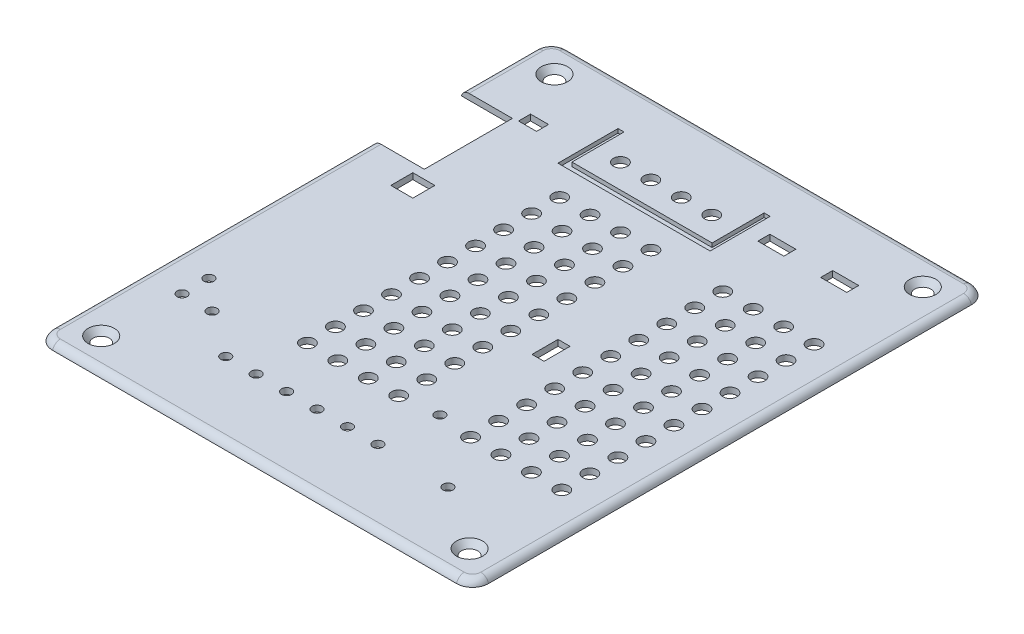
SolidWorks part; units mm, degrees
ref_plane "Přední rovina" through (0, 0, 0) normal (0, 0, 1) x (1, 0, 0)
ref_plane "Horní rovina" through (0, 0, 0) normal (0, 1, 0) x (1, 0, 0)
ref_plane "Pravá rovina" through (0, 0, 0) normal (1, 0, 0) x (0, 0, -1)
sketch "Skica1" plane through (0, 0, 0) normal (0, 1, 0) x (1, 0, 0)
  line L1 (-54.445, -64.3) -> (54.445, -64.3)
  line L2 (-54.445, -64.3) -> (-54.445, 64.3)
  line L3 (-54.445, 64.3) -> (54.445, 64.3)
  line L4 (54.445, -64.3) -> (54.445, 64.3)
  line L5 (-54.445, -64.3) -> (54.445, 64.3) construction
  line L6 (-54.445, 64.3) -> (54.445, -64.3) construction
  point P0 (0, 0)
  dimension "D1" = 108.89
  dimension "D2" = 128.6
extrude "Přidat vysunutím1" add sketch "Skica1" along normal blind 1.5
fillet "Zaoblit1" radius 4 4 edges at (54.445, 0.75, -64.3) (54.445, 0.75, 64.3) (-54.445, 0.75, -64.3) (-54.445, 0.75, 64.3)
fillet "Zaoblit2" radius 2 8 edges at (53.2734, 1.5, 63.1284) (0, 1.5, 64.3) (-53.2734, 1.5, 63.1284) (-54.445, 1.5, 0) (-53.2734, 1.5, -63.1284) (0, 1.5, -64.3) (53.2734, 1.5, -63.1284) (54.445, 1.5, 0)
sketch "Skica2" plane through (0, 0, 0) normal (0, -1, 0) x (1, 0, 0)
  line L0 (0, 68.8192) -> (0, -71.6902) construction
  line L1 (-80.8942, 0) -> (91.0271, 0) construction
  circle A0 centre (-46, 56.6) radius 1.6
  dimension "D1" = 3.2
  dimension "D2" = 46
  dimension "D3" = 56.6
extrude "Odebrat vysunutím1" cut sketch "Skica2" against normal blind 3
pattern_linear "LinPole1" count 2 spacing 113.2 along (0, 0, -1) count 2 spacing 92 along (1, 0, 0) of "Odebrat vysunutím1"
chamfer "Zkosení1" distance 2 angle 40 4 edges at (46, 1.5, 55) (46, 1.5, -58.2) (-46, 1.5, -58.2) (-46, 1.5, 55) first distance on face at (46, 0, 55) first distance on face at (46, 0, -58.2) first distance on face at (-46, 0, -58.2) first distance on face at (-46, 0, 55)
sketch "Skica3" plane through (0, 1.5, 0) normal (0, 1, 0) x (1, 0, 0)
  line L3 (-50, -50) -> (50, -50) construction
  line L4 (-50, -50) -> (-50, 50) construction
  line L5 (-50, 50) -> (50, 50) construction
  line L6 (50, -50) -> (50, 50) construction
  line L7 (-50, -50) -> (50, 50) construction
  line L8 (-50, 50) -> (50, -50) construction
  circle A0 centre (44.83, -32.38) radius 1.75
  circle A1 centre (4.08, -32.38) radius 1.75
  circle A2 centre (4.08, 45.8) radius 1.75
  point P7 (0, 0)
  dimension "D2" = 3.5
  dimension "D6" = 3.5
  dimension "D11" = 3.5
  dimension "D1" = 5.17
  dimension "D3" = 17.62
  dimension "D4" = 100
  dimension "D5" = 100
  dimension "D7" = 45.92
  dimension "D8" = 17.62
  dimension "D9" = 45.92
  dimension "D10" = 4.2
extrude "Odebrat vysunutím3" cut sketch "Skica3" against normal blind 4 contours A0 region at (44.83, 1.5, 32.38)
pattern_linear "LinPole3" count 10 spacing 7 along (0, 0, -1) count 4 spacing 7.6 along (-1, 0, 0) of "Odebrat vysunutím3"
extrude "Odebrat vysunutím4" cut sketch "Skica3<3>" against normal blind 4 contours A1 region at (4.08, 1.5, 32.38)
sketch "Skica3<3>" plane through (0, 1.5, 0) normal (0, 1, 0) x (1, 0, 0) same geometry as "Skica3"
pattern_linear "LinPole4" count 10 spacing 7 along (0, 0, -1) count 4 spacing 7.6 along (-1, 0, 0) of "Odebrat vysunutím4"
extrude "Odebrat vysunutím5" cut sketch "Skica3<4>" against normal blind 10
sketch "Skica3<4>" plane through (0, 1.5, 0) normal (0, 1, 0) x (1, 0, 0) same geometry as "Skica3"
pattern_linear "LinPole5" count 4 spacing 7.6 along (-1, 0, 0) of "Odebrat vysunutím5"
sketch "Skica4" plane through (0, 1.5, 0) normal (0, 1, 0) x (1, 0, 0)
  line L1 (-50, -50) -> (50, -50) construction
  line L2 (-50, -50) -> (-50, 50) construction
  line L3 (-50, 50) -> (50, 50) construction
  line L4 (50, -50) -> (50, 50) construction
  line L5 (-50, -50) -> (50, 50) construction
  line L6 (-50, 50) -> (50, -50) construction
  line L7 (15.5, 48.9) -> (22, 48.9)
  line L8 (15.5, 48.9) -> (15.5, 45.9)
  line L9 (15.5, 45.9) -> (22, 45.9)
  line L10 (22, 48.9) -> (22, 45.9)
  line L11 (15.5, 48.9) -> (22, 45.9) construction
  line L12 (15.5, 45.9) -> (22, 48.9) construction
  line L13 (31.2, 48.9) -> (37.7, 48.9)
  line L14 (31.2, 48.9) -> (31.2, 45.9)
  line L15 (31.2, 45.9) -> (37.7, 45.9)
  line L16 (37.7, 48.9) -> (37.7, 45.9)
  line L17 (31.2, 48.9) -> (37.7, 45.9) construction
  line L18 (31.2, 45.9) -> (37.7, 48.9) construction
  line L19 (11.8, -0.3) -> (14.8, -0.3)
  line L20 (11.8, -0.3) -> (11.8, -6.8)
  line L21 (11.8, -6.8) -> (14.8, -6.8)
  line L22 (14.8, -0.3) -> (14.8, -6.8)
  line L23 (11.8, -0.3) -> (14.8, -6.8) construction
  line L24 (11.8, -6.8) -> (14.8, -0.3) construction
  circle A0 centre (13.38, -31.4) radius 1.25
  circle A2 centre (30, -46) radius 1.25
  circle A3 centre (-45, -37.4) radius 1.25
  circle A4 centre (-45, -30.7) radius 1.25
  circle A5 centre (-37.52, -37.4) radius 1.25
  point P0 (0, 0)
  point P6 (18.75, 47.4)
  point P11 (34.45, 47.4)
  point P16 (13.3, -3.55)
  point P21 (13.3, -0.3)
  dimension "D13" = 2.5
  dimension "D16" = 12.48
  dimension "D17" = 2.5
  dimension "D23" = 2.5
  dimension "D24" = 2.5
  dimension "D25" = 2.5
  dimension "D1" = 100
  dimension "D2" = 100
  dimension "D3" = 3
  dimension "D4" = 6.5
  dimension "D5" = 1.1
  dimension "D6" = 1.1
  dimension "D7" = 12.3
  dimension "D8" = 28
  dimension "D9" = 35.2
  dimension "D10" = 50.3
  dimension "D11" = 36.62
  dimension "D12" = 18.6
  dimension "D14" = 5
  dimension "D15" = 5
  dimension "D18" = 20
  dimension "D19" = 4
  dimension "D20" = 80.7
  dimension "D21" = 87.4
  dimension "D22" = 87.4
extrude "Odebrat vysunutím6" cut sketch "Skica4" against normal blind 10
sketch "Skica5" plane through (0, 1.5, 0) normal (0, 1, 0) x (1, 0, 0)
  line L1 (-50, 50) -> (50, 50) construction
  line L2 (-50, 50) -> (-50, -50) construction
  line L3 (-50, -50) -> (50, -50) construction
  line L4 (50, 50) -> (50, -50) construction
  line L5 (-50, 50) -> (50, -50) construction
  line L6 (-50, -50) -> (50, 50) construction
  circle A0 centre (-26, -45.5) radius 1.25
  point P0 (0, 0)
  dimension "D5" = 2.5
  dimension "D1" = 100
  dimension "D2" = 100
  dimension "D3" = 4.5
  dimension "D4" = 76
extrude "Odebrat vysunutím7" cut sketch "Skica5" against normal blind 10
pattern_linear "LinPole6" count 6 spacing 7.6 along (1, 0, 0) of "Odebrat vysunutím7"
sketch "Skica6" plane through (0, 1.5, 0) normal (0, 1, 0) x (1, 0, 0)
  line L1 (-42.39, 17.62) -> (-36.89, 17.62)
  line L2 (-42.39, 17.62) -> (-42.39, 12.12)
  line L3 (-42.39, 12.12) -> (-36.89, 12.12)
  line L4 (-36.89, 17.62) -> (-36.89, 12.12)
  line L5 (-42.39, 17.62) -> (-36.89, 12.12) construction
  line L6 (-42.39, 12.12) -> (-36.89, 17.62) construction
  line L7 (-41.7, 41.8) -> (-63.2133, 41.8)
  line L8 (-41.7, 41.8) -> (-41.7, 19.8)
  line L9 (-41.7, 19.8) -> (-63.2133, 19.8)
  line L10 (-63.2133, 41.8) -> (-63.2133, 19.8)
  line L11 (-41.7, 41.8) -> (-63.2133, 19.8) construction
  line L12 (-41.7, 19.8) -> (-63.2133, 41.8) construction
  line L14 (-50, 50) -> (50, 50) construction
  line L15 (-50, 50) -> (-50, -50) construction
  line L16 (-50, -50) -> (50, -50) construction
  line L17 (50, 50) -> (50, -50) construction
  line L18 (-50, 50) -> (50, -50) construction
  line L19 (-50, -50) -> (50, 50) construction
  line L20 (-40.37, 45) -> (-35.87, 45)
  line L21 (-40.37, 45) -> (-40.37, 42)
  line L22 (-40.37, 42) -> (-35.87, 42)
  line L23 (-35.87, 45) -> (-35.87, 42)
  line L24 (-40.37, 45) -> (-35.87, 42) construction
  line L25 (-40.37, 42) -> (-35.87, 45) construction
  point P0 (-39.64, 14.87)
  point P5 (-52.4567, 30.8)
  point P10 (-63.2133, 19.8)
  point P12 (0, 0)
  point P18 (-52.4567, 41.8)
  point P20 (-38.12, 43.5)
  dimension "D1" = 100
  dimension "D2" = 100
  dimension "D3" = 10.36
  dimension "D4" = 35.13
  dimension "D5" = 5.5
  dimension "D6" = 8.2
  dimension "D7" = 30.2
  dimension "D8" = 8.3
  dimension "D9" = 6.5
  dimension "D10" = 11.88
  dimension "D11" = 4.5
  dimension "D12" = 3
extrude "Odebrat vysunutím8" cut sketch "Skica6" against normal blind 10 contours L4 L1 L2 L3 | L23 L20 L21 L22 | L7 L10 L9 L8 region at (-39.64, 1.5, -14.87) region at (-38.12, 1.5, -43.5)
sketch "Skica7" plane through (0, 1.5, 0) normal (0, 1, 0) x (1, 0, 0)
  line L1 (-24.82, 39.8) -> (10.18, 39.8)
  line L2 (-24.82, 39.8) -> (-24.82, 37.8)
  line L3 (-24.82, 37.8) -> (10.18, 37.8)
  line L4 (10.18, 39.8) -> (10.18, 37.8)
  line L5 (-26.32, 52.8) -> (-24.82, 52.8)
  line L6 (-26.32, 52.8) -> (-26.32, 37.8)
  line L7 (-26.32, 37.8) -> (-24.82, 37.8)
  line L8 (-24.82, 52.8) -> (-24.82, 37.8)
  line L9 (11.68, 52.8) -> (10.18, 52.8)
  line L10 (11.68, 52.8) -> (11.68, 37.8)
  line L11 (11.68, 37.8) -> (10.18, 37.8)
  line L12 (10.18, 52.8) -> (10.18, 37.8)
  circle A0 centre (-11.12, 45.8) radius 1.75 construction
  circle A1 centre (-18.72, 45.8) radius 1.75 construction
  dimension "D2" = 6
  dimension "D6" = 2
  dimension "D1" = 35
  dimension "D3" = 15
  dimension "D4" = 1.5
  dimension "D5" = 6.1
extrude "Odebrat vysunutím9" cut sketch "Skica7" against normal blind 1 contours L4 L1 L2 L3 | L8 L5 L6 L7 L2 | L9 L12 L4 L11 L10 region at (-7.32, 1.5, -38.8) region at (-25.57, 1.5, -45.3) region at (10.93, 1.5, -45.3)
